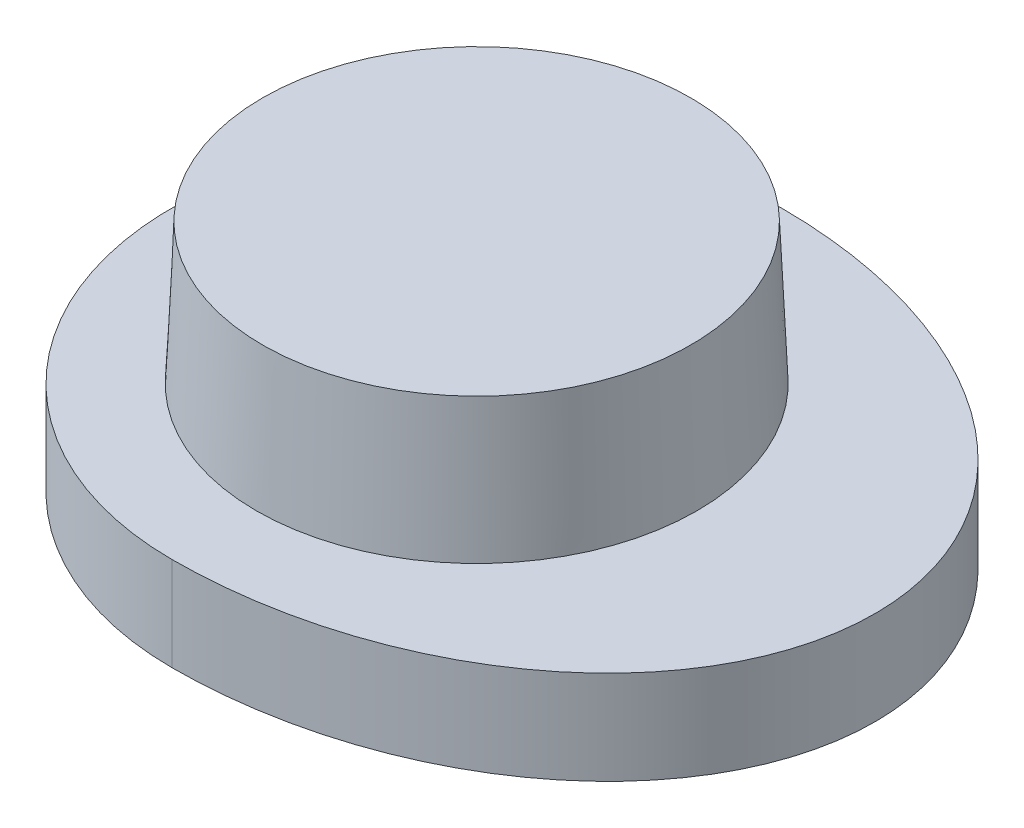
SolidWorks part; units mm, degrees
ref_plane "Front Plane" through (0, 0, 0) normal (0, 0, 1) x (1, 0, 0)
ref_plane "Top Plane" through (0, 0, 0) normal (0, 1, 0) x (1, 0, 0)
ref_plane "Right Plane" through (0, 0, 0) normal (1, 0, 0) x (0, 0, -1)
sketch "Sketch1" plane through (0, 0, 0) normal (0, 0, 1) x (1, 0, 0)
  line L0 (-4.7, 0) -> (-6.5, 0)
  line L1 (-6.5, 0) -> (-6.5, -2)
  line L2 (-6.5, -2) -> (-5.5826, -2)
  line L3 (-5.5826, -2) -> (-5.4255, -20)
  line L4 (-5.4255, -20) -> (-2.35, -23.0755)
  line L5 (0, 0) -> (0, -78.5552) construction
  line L6 (-4.6826, -1.9921) -> (-4.5287, -19.624)
  line L8 (-4.6826, -1.9921) -> (-4.7, 0)
  line L10 (4.6826, -1.9921) -> (4.7, 0)
  line L11 (4.7, 0) -> (6.5, 0)
  line L12 (6.5, -2) -> (5.5826, -2)
  line L13 (5.5826, -2) -> (5.4255, -20)
  line L14 (4.6826, -1.9921) -> (4.5287, -19.624)
  line L16 (5.4255, -20) -> (2.35, -23.0755)
  line L17 (5.5826, -2) -> (5.5826, -11.7732) construction
  line L18 (22, 17.9555) -> (22, -54.2112) construction
  line L19 (6.5, -2) -> (18, -2)
  line L20 (18, -2) -> (18, 2)
  line L21 (18, 2) -> (26, 2)
  line L22 (26.569, 3) -> (17.431, 3)
  line L23 (17.431, 3) -> (17.3, 0)
  line L24 (17.3, 0) -> (15.5, 0)
  line L26 (14, -1.5) -> (8, -1.5)
  line L27 (17.3, 0) -> (17.3, 13.958) construction
  line L28 (26.569, 3) -> (26.7, 0)
  line L29 (26, -2) -> (26, 2)
  line L31 (26.7, 0) -> (28.5, 0)
  line L33 (26, -2) -> (28.5, -2)
  line L34 (28.5, 0) -> (28.5, -2)
  line L36 (5.5826, -2) -> (5.5826, 0)
  line L37 (17.3, 0) -> (17.3, -2)
  line L38 (15.5, 0) -> (6.5, 0)
  line L40 (22, 2) -> (22, 3)
  line L41 (6.5, 0) -> (6.5, -2)
  line L43 (-2.35, -24.5755) -> (-2.35, -23.0755)
  line L44 (-4.5287, -19.624) -> (-1.7136, -22.4391) construction
  line L45 (-1.45, -24.5755) -> (-1.45, -22.7027)
  line L46 (-4.5287, -19.624) -> (-1.45, -22.7027)
  line L47 (-4.6904, -1.1) -> (-4.5287, -19.624)
  line L48 (-5.6, -1.1) -> (-4.6904, -1.1)
  line L49 (-5.6, -0.9) -> (-5.6, -1.1)
  line L50 (-5.5922, -0.9) -> (-5.6, -0.9)
  line L51 (-5.5826, -2) -> (-5.5922, -0.9)
  line L52 (-5.5826, -2) -> (-5.4287, -19.6318)
  line L53 (-2.35, -24.5755) -> (-1.45, -24.5755)
  arc A2 (-2.35, -23.0755) -> (1.5642, -23.1585) centre (-0.3496, -21.0751) ccw construction
  arc A4 (-1.7136, -22.4391) -> (0.9553, -22.4957) centre (-0.3496, -21.0751) ccw construction
  arc A6 (6.5, 0) -> (8, -1.5) centre (8, 0) ccw
  arc A7 (15.5, 0) -> (14, -1.5) centre (14, 0) cw
  point P44 (22, 3)
  point P46 (22, 2)
  dimension "D9" = 22
  dimension "D17" = 1.5
  dimension "D18" = 1.5
  dimension "D16" = 13
  dimension "D1" = 0.9
  dimension "D2" = 2
  dimension "D3" = 20
  dimension "D4" = 9.4
  dimension "D5" = 13
  dimension "D6" = 0.9
  dimension "D7" = 0.5
  dimension "D8" = 45
  dimension "D10" = 4
  dimension "D11" = 5
  dimension "D12" = 2.5
  dimension "D13" = 0.5
  dimension "D14" = 9.4
  dimension "D15" = 8
  dimension "D19" = 1.45
revolve "Revolve25" add sketch "Sketch1" angle 360 about L5 region at (-5.7282, -0.8433, 0) region at (-4.9249, -1.5482, 0)
revolve "Revolve31" add sketch "Sketch1<10>" angle 360 about L18 region at (24.2845, 2.918, 0)
sketch "Sketch1<10>" plane through (0, 0, 0) normal (0, 0, 1) x (1, 0, 0) same geometry as "Sketch1"
ref_plane "Plane1" through (0, -2, 0) normal (0, -1, 0) x (-1, 0, 0)
sketch "Sketch2" plane through (0, -2, 0) normal (0, -1, 0) x (-1, 0, 0)
  line L0 (-22, 6.5) -> (-22, 4)
  line L1 (-22, -6.5) -> (-22, -4)
  line L3 (-14.8455, 1.25) -> (-7.1545, 1.25)
  line L5 (-14.8455, -1.25) -> (-7.1545, -1.25)
  line L8 (-7.1545, 1.25) -> (-7.1545, -1.25)
  line L9 (-14.8455, -1.25) -> (-14.8455, 1.25)
  line L10 (-15.7994, -1.95) -> (-15.7994, 1.95)
  line L11 (-6.2006, 1.95) -> (-6.2006, -1.95)
  circle A0 centre (-22, 0) radius 6.5 construction
  circle A1 centre (-22, 0) radius 4 construction
  arc A2 (-22, -4) -> (-22, 4) centre (-22, 0) cw
  arc A3 (-22, 6.5) -> (-15.7994, 1.95) centre (-22, 0) cw
  arc A4 (-14.8455, 1.25) -> (-15.7994, 1.95) centre (-14.8455, 2.25) cw
  arc A5 (-22, -6.5) -> (-15.7994, -1.95) centre (-22, 0) ccw
  arc A6 (-14.8455, -1.25) -> (-15.7994, -1.95) centre (-14.8455, -2.25) ccw
  arc A7 (0, 6.5) -> (-6.2006, 1.95) centre (0, 0) ccw
  circle A8 centre (0, 0) radius 6.5 construction
  arc A9 (-6.2006, 1.95) -> (-7.1545, 1.25) centre (-7.1545, 2.25) cw
  arc A10 (0, -6.5) -> (-6.2006, -1.95) centre (0, 0) cw
  arc A11 (-7.1545, -1.25) -> (-6.2006, -1.95) centre (-7.1545, -2.25) cw
  ellipse E0 centre (-22, 0) end of major axis (-13.5, 0) minor radius 6.5
  point P1 (-22, 6.5)
  point P7 (-22, -6.5)
  dimension "D2" = 1
  dimension "D3" = 1
  dimension "D4" = 6.5
  dimension "D7" = 2.5
  dimension "D5" = 1
  dimension "D6" = 1
  dimension "D1" = 8.5
extrude "Boss-Extrude4" add sketch "Sketch2" against normal up to surface (2 mm away) contours L0 E0 L1 A2 region at (26.3861, -2, 0) up to face at (15.5, 0, 0)
delete or keep bodies "Body-Delete/Keep 1" type delete bodies bodies 102
scale "Scale1" bodies to scale 106 scale about centroid uniform scaling yes scale factor 0.854545
